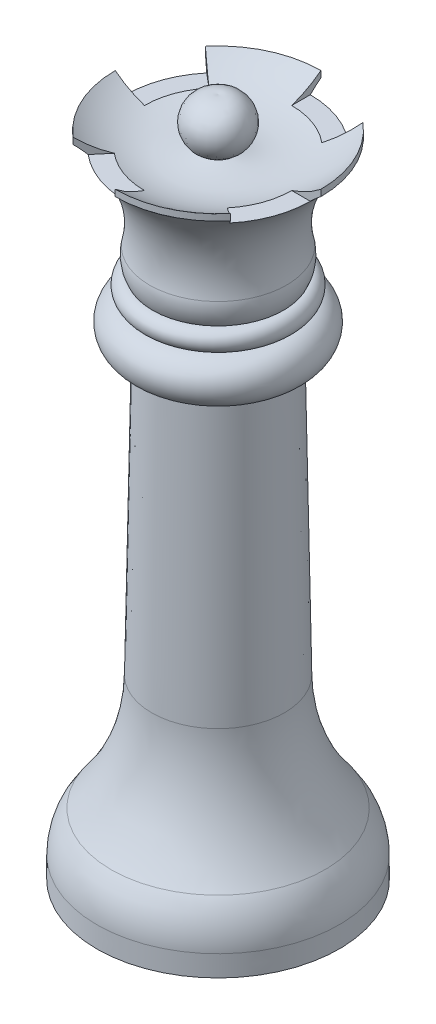
SolidWorks part; units mm, degrees
material "PVC Rigid"
ref_plane "Front Plane" through (0, 0, 0) normal (0, 0, 1) x (1, 0, 0)
ref_plane "Top Plane" through (0, 0, 0) normal (0, 1, 0) x (1, 0, 0)
ref_plane "Right Plane" through (0, 0, 0) normal (1, 0, 0) x (0, 0, -1)
sketch "Sketch1" plane through (0, 0, 0) normal (0, 0, 1) x (1, 0, 0)
  line L0 (0, 0) -> (-11.6, 0)
  line L3 (-11.5897, 2) -> (-11.6, 0)
  line L32 (0, 65) -> (0, 0)
  line L33 (-5.8734, 44.12) -> (-6.3432, 44.12)
  line L34 (-6.3432, 16.936) -> (-5.8734, 44.12)
  line L35 (-9.8373, 61.4466) -> (-9.8373, 62.061)
  line L36 (0, 0) -> (0, 50) construction
  arc A0 (-10.2296, 5.8838) -> (-11.5897, 2) centre (-5.271, 1.9673) ccw
  circle A32 centre (0, 62.5962) radius 2.4038 construction
  arc A34 (0, 65) -> (-1.2079, 60.5179) centre (-0.4218, 62.7099) ccw
  arc A36 (-6.3432, 44.12) -> (-6.2866, 48.2698) centre (-6.3432, 46.1953) cw
  arc A39 (-9.8373, 61.4466) -> (-6.5463, 52.467) centre (-15.0641, 54.4381) cw
  arc A40 (-10.2296, 5.8838) -> (-6.3432, 16.936) centre (-24.3998, 17.076) ccw
  arc A42 (-9.8373, 62.061) -> (-1.2079, 60.5179) centre (-4.0599, 69.4691) ccw
  arc A43 (-6.2866, 48.2698) -> (-6.2597, 50.24) centre (-6.2598, 49.2547) cw
  arc A44 (-6.5463, 52.467) -> (-6.2597, 50.24) centre (-3.4026, 51.7396) ccw
  dimension "D2" = 5.8734
  dimension "D6" = 4.1499
  dimension "D4" = 65
  dimension "D8" = 3.2268
  dimension "D9" = 8.7429
  dimension "D11" = 16.3979
  dimension "D13" = 20.88
  dimension "D15" = 17.941
  dimension "D16" = 2.0753
  dimension "D17" = 6.2866
  dimension "D19" = 8.3471
  dimension "D23" = 10.2296
  dimension "D21" = 5.8838
  dimension "D18" = 6.5463
  dimension "D20" = 9.3945
  dimension "D35" = 2.3287
  dimension "D7" = 0.9853
  dimension "D22" = 6.3187
  dimension "D1" = 2
  dimension "D5" = 11.6
  dimension "D10" = 0.6144
  dimension "D12" = 1.2079
  dimension "D14" = 8.6293
revolve "Revolve6" add sketch "Sketch1" angle 360 about L32 region at (-3.7198, 29.0748, 0)
sketch "Sketch10" plane through (0, 0, 0) normal (0, 0, 1) x (1, 0, 0)
  line L0 (-9.8373, 60.561) -> (-9.8373, 62.061) construction
  line L1 (-14.5937, 60.561) -> (-5.0809, 60.561)
  line L2 (-14.5937, 60.561) -> (-14.5937, 72.2832)
  line L3 (-14.5937, 72.2832) -> (-5.0809, 72.2832)
  line L4 (-5.0809, 60.561) -> (-5.0809, 72.2832)
  dimension "D1" = 1.5
revolve "Cut-Revolve8" cut sketch "Sketch10" angle 40 about L36 reverse direction yes
sketch "Sketch11" plane through (0, 0, 0) normal (0, 0, 1) x (1, 0, 0)
  line L0 (9.8373, 60.561) -> (9.8373, 62.061) construction
  line L1 (6.3584, 60.561) -> (13.3161, 60.561)
  line L2 (6.3584, 60.561) -> (6.3584, 71.1571)
  line L3 (6.3584, 71.1571) -> (13.3161, 71.1571)
  line L4 (13.3161, 60.561) -> (13.3161, 71.1571)
  line L5 (-9.8373, 62.061) -> (9.8373, 62.061) construction
  dimension "D1" = 1.5
revolve "Cut-Revolve9" cut sketch "Sketch11" angle 40 about L36 reverse direction yes
sketch "Sketch12" plane through (0, 0, 0) normal (1, 0, 0) x (0, 0, -1)
  line L0 (9.8373, 60.561) -> (9.8373, 62.061) construction
  line L1 (5.2356, 60.561) -> (14.4389, 60.561)
  line L2 (5.2356, 60.561) -> (5.2356, 72.223)
  line L3 (5.2356, 72.223) -> (14.4389, 72.223)
  line L4 (14.4389, 60.561) -> (14.4389, 72.223)
  line L5 (0, 62.061) -> (9.8373, 62.061) construction
  dimension "D1" = 1.5
revolve "Cut-Revolve10" cut sketch "Sketch12" angle 40 about L36 reverse direction yes
sketch "Sketch13" plane through (0, 0, 0) normal (1, 0, 0) x (0, 0, -1)
  line L0 (-9.8373, 60.561) -> (-9.8373, 62.061) construction
  line L1 (-14.1563, 60.561) -> (-5.5182, 60.561)
  line L2 (-14.1563, 60.561) -> (-14.1563, 72.4481)
  line L3 (-14.1563, 72.4481) -> (-5.5182, 72.4481)
  line L4 (-5.5182, 60.561) -> (-5.5182, 72.4481)
  line L5 (0, 62.061) -> (-9.8373, 62.061) construction
  dimension "D1" = 1.5
revolve "Cut-Revolve11" cut sketch "Sketch13" angle 40 about L36 reverse direction yes
sketch "Sketch8" plane through (0, 0, 0) normal (0, -1, 0) x (1, 0, 0)
  circle A0 centre (0, 0) radius 10
extrude "Cut-Extrude1" cut sketch "Sketch8" against normal blind 2 from offset 0.4 offset against normal yes
